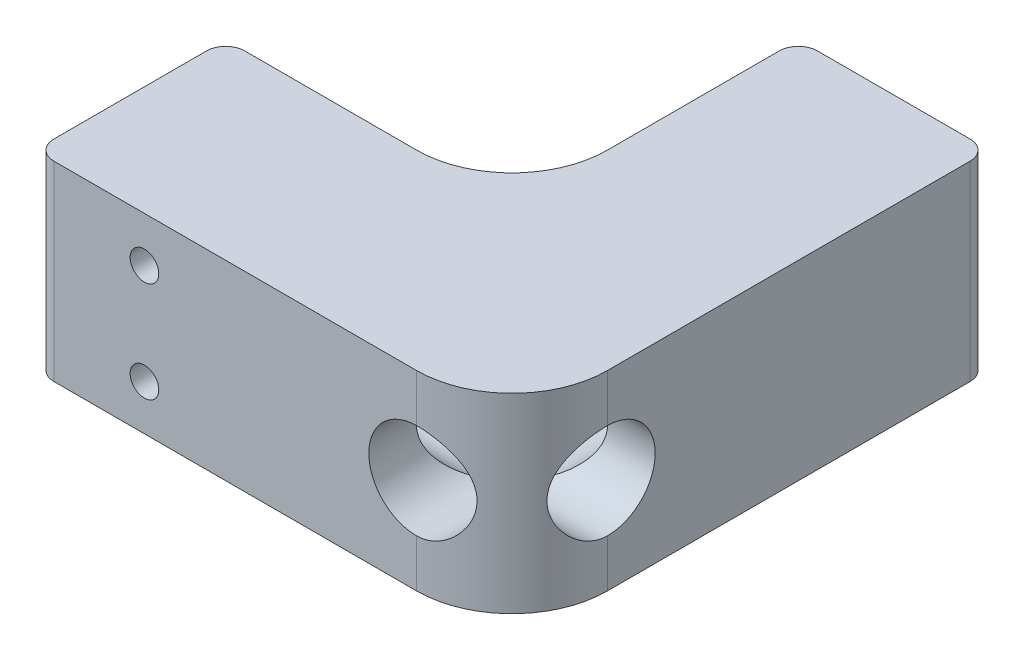
SolidWorks part; units mm, degrees
ref_plane "Front Plane" through (0, 0, 0) normal (0, 0, 1) x (1, 0, 0)
ref_plane "Top Plane" through (0, 0, 0) normal (0, 1, 0) x (1, 0, 0)
ref_plane "Right Plane" through (0, 0, 0) normal (1, 0, 0) x (0, 0, -1)
sketch "Sketch1" plane through (0, 0, 0) normal (0, 1, 0) x (1, 0, 0)
  line L0 (-10, 30) -> (10, 30)
  line L1 (10, 30) -> (10, -20)
  line L2 (10, -20) -> (-40, -20)
  line L3 (-40, -20) -> (-40, 0)
  line L4 (-40, 0) -> (-10, 0)
  line L5 (-10, 0) -> (-10, 30)
  line L6 (0, -11) -> (0, 11) construction
  line L7 (-11, 0) -> (11, 0) construction
  point P2 (0, 30)
  dimension "D1" = 20
  dimension "D2" = 90
  dimension "D3" = 30
extrude "Boss-Extrude1" add sketch "Sketch1" along normal mid plane 20
sketch "Sketch2" plane through (0, 0, -30) normal (0, 0, -1) x (-1, 0, 0)
  circle A0 centre (0, 0) radius 2.25
  dimension "D1" = 4.5
extrude "Cut-Extrude1" cut sketch "Sketch2" against normal through all
sketch "Sketch3" plane through (-40, 0, 0) normal (-1, 0, 0) x (0, 0, 1)
  line L0 (0, 10) -> (20, -10) construction
  circle A0 centre (10, 0) radius 2.25
  dimension "D1" = 4.5
extrude "Cut-Extrude2" cut sketch "Sketch3" against normal through all
ref_plane "Plane1" through (0, 0, 20) normal (0, 0, 1) x (1, 0, 0)
sketch "Sketch5" plane through (0, 0, 20) normal (0, 0, 1) x (1, 0, 0)
  circle A0 centre (0, 0) radius 5
  dimension "D1" = 10
extrude "Cut-Extrude3" cut sketch "Sketch5" against normal offset from surface (42 mm away) 8 up to face at (-2.25, 0, -30)
ref_plane "Plane2" through (10, 0, 0) normal (-1, 0, 0) x (0, 0, 1)
sketch "Sketch6" plane through (10, 0, 0) normal (-1, 0, 0) x (0, 0, 1)
  circle A0 centre (10, 0) radius 5
  circle A1 centre (10, 0) radius 2.25 construction
  dimension "D1" = 10
extrude "Cut-Extrude4" cut sketch "Sketch6" along normal offset from surface (42 mm away) 8 up to face at (-40, 0, 12.25)
chamfer "Chamfer1" distance 2.75 angle 45 2 edges at (-32, 0, 7.75) (2.25, 0, -22)
fillet "Fillet1" radius 10 2 edges at (-10, 0, 0) (10, 0, 20)
fillet "Fillet2" radius 2 4 edges at (-10, 0, -30) (10, 0, -30) (-40, 0, 0) (-40, 0, 20)
sketch "Sketch8" plane through (0, 0, 20) normal (0, 0, 1) x (1, 0, 0)
  line L0 (-38, 0) -> (-19.0183, 0)
  line L1 (-38, 10) -> (-38, -10) construction
  line L2 (27.5, 0) -> (-27.5, 0) construction
  line L3 (-28.5092, 0) -> (-28.5092, 5.2634)
  circle A0 centre (-28.5092, 5.2634) radius 1.5
  circle A1 centre (-28.5092, -5.2634) radius 1.5
  dimension "D1" = 3
extrude "Cut-Extrude5" cut sketch "Sketch8" against normal blind 28 contours A0 | A1 region at (-27.4785, 4.2328, 20) region at (-28.5092, -5.2634, 20)
